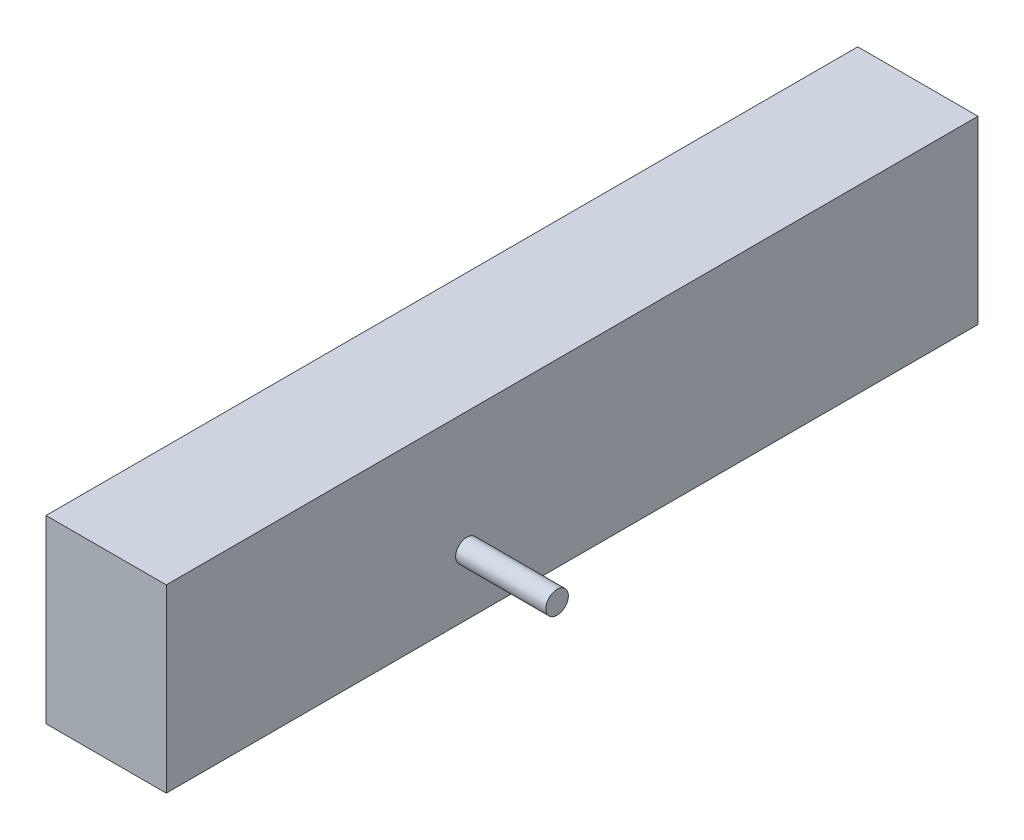
SolidWorks part; units mm, degrees
ref_plane "Front Plane" through (0, 0, 0) normal (0, 0, 1) x (1, 0, 0)
ref_plane "Top Plane" through (0, 0, 0) normal (0, 1, 0) x (1, 0, 0)
ref_plane "Right Plane" through (0, 0, 0) normal (1, 0, 0) x (0, 0, -1)
sketch "Sketch1" plane through (0, 0, 0) normal (1, 0, 0) x (0, 0, -1)
  circle A0 centre (0, 0) radius 9.525
  dimension "D1" = 19.05
extrude "Boss-Extrude1" add sketch "Sketch1" along normal mid plane 254
sketch "Sketch2" plane through (0, 0, 0) normal (1, 0, 0) x (0, 0, -1)
  line L1 (-254, -50.8) -> (431.8, -50.8)
  line L2 (-254, -50.8) -> (-254, 101.6)
  line L3 (-254, 101.6) -> (431.8, 101.6)
  line L4 (431.8, -50.8) -> (431.8, 101.6)
  point P4 (-312.7155, -50.8)
  dimension "D1" = 152.4
  dimension "D2" = 685.8
  dimension "D3" = 50.8
  dimension "D4" = 254
extrude "Boss-Extrude2" add sketch "Sketch2" along normal mid plane 101.6
